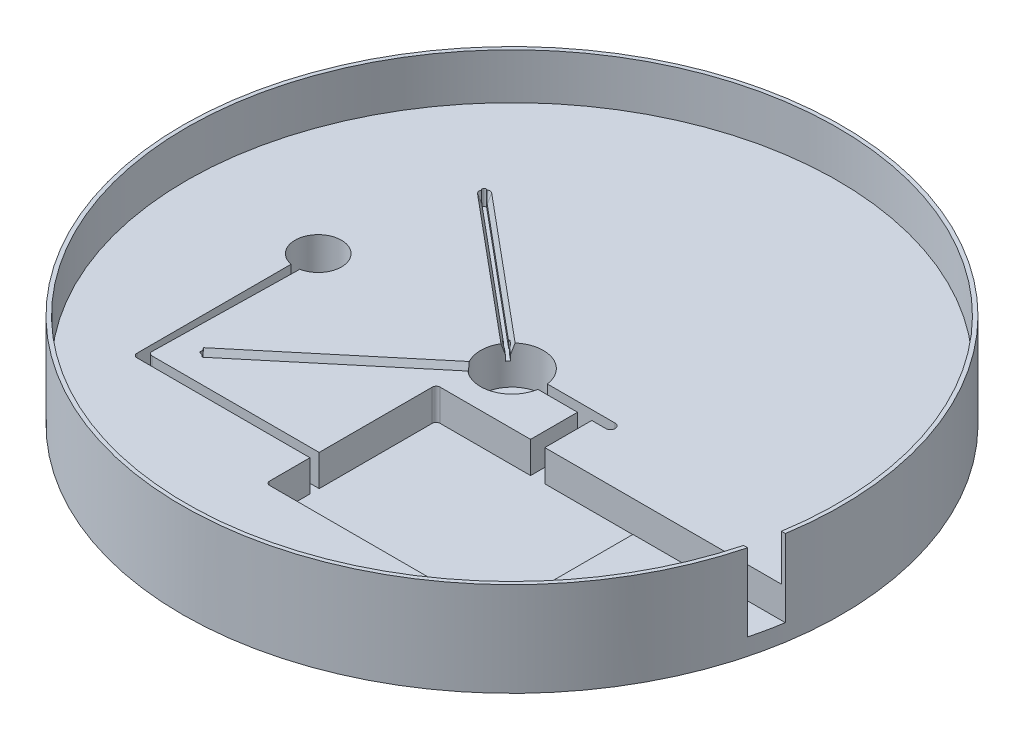
SolidWorks part; units mm, degrees
ref_plane "Front Plane" through (0, 0, 0) normal (0, 0, 1) x (1, 0, 0)
ref_plane "Top Plane" through (0, 0, 0) normal (0, 1, 0) x (1, 0, 0)
ref_plane "Right Plane" through (0, 0, 0) normal (1, 0, 0) x (0, 0, -1)
sketch "Sketch1" plane through (0, 0, 0) normal (0, 1, 0) x (1, 0, 0)
  circle A0 centre (0, 0) radius 266.7
extrude "Boss-Extrude1" add sketch "Sketch1" along normal blind 76.2
sketch "Sketch2" plane through (0, 76.2, 0) normal (0, 1, 0) x (1, 0, 0)
  circle A0 centre (0, 0) radius 263.525
extrude "Cut-Extrude1" cut sketch "Sketch2" against normal blind 37.084
sketch "Sketch3" plane through (0, 39.116, 0) normal (0, 1, 0) x (1, 0, 0)
  circle A0 centre (0, 0) radius 25.4
extrude "Cut-Extrude2" cut sketch "Sketch3" against normal blind 30.988
sketch "Sketch4" plane through (0, 39.116, 0) normal (0, 1, 0) x (1, 0, 0)
  line L0 (3.81, -0.2983) -> (80.01, -0.2983) construction
  line L1 (0, 3.5117) -> (76.2, 3.5117) construction
  line L2 (0, 3.5117) -> (0, -4.1083) construction
  line L3 (0, -4.1083) -> (76.2, -4.1083) construction
  line L4 (76.2, 3.5117) -> (76.2, -4.1083) construction
  line L5 (3.81, 3.5117) -> (80.01, 3.5117)
  line L6 (3.81, -4.1083) -> (80.01, -4.1083)
  line L7 (0, 3.5117) -> (0, -4.1083) construction
  arc A0 (3.81, 3.5117) -> (3.81, -4.1083) centre (3.81, -0.2983) ccw
  arc A1 (80.01, -4.1083) -> (80.01, 3.5117) centre (80.01, -0.2983) ccw
  point P6 (41.91, -0.2983)
extrude "Cut-Extrude3" cut sketch "Sketch4" against normal through all
sketch "Sketch5" plane through (0, 39.116, 0) normal (0, 1, 0) x (1, 0, 0)
  line L0 (0, 0) -> (-39.9134, 33.31) construction
  line L1 (-39.9134, 33.31) -> (-39.9134, -33.31) construction
  line L2 (-39.9134, 0) -> (-42.73, -2.8166) construction
  line L3 (0, 0) -> (-39.9134, 0) construction
  line L4 (-39.9134, 0) -> (-42.73, 2.8166) construction
  line L5 (0, 0) -> (-39.9134, -33.31) construction
  line L6 (0, 0) -> (-136.5075, 113.9234) construction
  line L7 (-0.9765, -1.1701) -> (-137.484, 112.7533)
  line L8 (0.9765, 1.1701) -> (-135.5311, 115.0934)
  line L13 (0, 0) -> (-136.5075, -113.9234) construction
  line L14 (-136.5075, -113.9234) -> (0, 0) construction
  line L15 (-137.484, -112.7533) -> (-0.9765, 1.1701)
  line L16 (-135.5311, -115.0934) -> (0.9765, -1.1701)
  arc A0 (-0.9765, -1.1701) -> (0.9765, 1.1701) centre (0, 0) ccw
  arc A1 (-135.5311, 115.0934) -> (-137.484, 112.7533) centre (-136.5075, 113.9234) ccw
  arc A4 (-137.484, -112.7533) -> (-135.5311, -115.0934) centre (-136.5075, -113.9234) ccw
  arc A5 (0.9765, -1.1701) -> (-0.9765, 1.1701) centre (0, 0) ccw
  point P7 (-68.2538, 56.9617)
  point P24 (-68.2538, -56.9617)
  arc M12 (25.0655, -4.1083) -> (25.1561, 3.5117) centre (0, 0) cw
extrude "Cut-Extrude4" cut sketch "Sketch5" against normal blind 12.7 contours L15 A4 L16 M12 | L7 A1 L8 A0 region at (-78.4582, 39.116, 65.4779)
ref_plane "Plane1" through (-19.4659, 0, -16.2454) normal (0.7678, 0, 0.6407) x (0.6407, 0, -0.7678)
sketch "Sketch6" plane through (-19.4659, 0, -16.2454) normal (0.7678, 0, 0.6407) x (0.6407, 0, -0.7678)
  line L0 (0, 26.416) -> (-4.0671, 39.116)
  line L1 (1.524, 26.416) -> (-1.524, 26.416) construction
  line L2 (-1.524, 39.116) -> (-24.6725, 39.116) construction
  line L3 (-4.0671, 39.116) -> (4.0671, 39.116)
  line L4 (1.524, 39.116) -> (-1.524, 39.116) construction
  line L5 (0, 39.116) -> (0, 26.416) construction
  line L6 (0, 26.416) -> (4.0671, 39.116)
extrude "Cut-Extrude5" cut sketch "Sketch6" against normal blind 152.4 and the other way blind 6.35
ref_plane "Plane2" through (-19.4659, 0, 16.2454) normal (-0.7678, 0, 0.6407) x (0.6407, 0, 0.7678)
sketch "Sketch11" plane through (-19.4659, 0, 16.2454) normal (-0.7678, 0, 0.6407) x (0.6407, 0, 0.7678)
  line L0 (0, 26.416) -> (4.7515, 39.116)
  line L1 (1.524, 26.416) -> (-1.524, 26.416) construction
  line L2 (263.525, 39.116) -> (-263.525, 39.116) construction
  line L3 (4.7515, 39.116) -> (-4.7515, 39.116)
  line L5 (0, 39.4107) -> (0, 26.416) construction
  line L7 (0, 26.416) -> (-4.7515, 39.116)
extrude "Cut-Extrude6" cut sketch "Sketch11" along normal blind 152.4 and the other way blind 6.35
ref_plane "Plane3" through (-24.3412, 0, 20.3141) normal (-0.7678, 0, 0.6407) x (0.6407, 0, 0.7678)
sketch "Sketch12" plane through (-24.3412, 0, 20.3141) normal (-0.7678, 0, 0.6407) x (0.6407, 0, 0.7678)
  line L0 (0, 26.416) -> (0, 31.0485) construction
  line L1 (1.524, 26.416) -> (-1.524, 26.416) construction
  line L2 (2.159, 26.416) -> (-2.159, 26.416) construction
  line L4 (-2.159, 26.416) -> (2.159, 26.416)
  line L7 (-2.159, 26.416) -> (-2.159, 41.4963)
  line L8 (-2.159, 41.4963) -> (2.159, 41.4963)
  line L9 (2.159, 26.416) -> (2.159, 41.4963)
extrude "Cut-Extrude10" cut sketch "Sketch12" along normal blind 6.35
ref_plane "Plane4" through (-24.3412, 0, -20.3141) normal (0.7678, 0, 0.6407) x (0.6407, 0, -0.7678)
sketch "Sketch14" plane through (-24.3412, 0, -20.3141) normal (0.7678, 0, 0.6407) x (0.6407, 0, -0.7678)
  line L0 (-2.159, 39.116) -> (2.159, 39.116) construction
  line L1 (0, 26.416) -> (-2.159, 26.416) construction
  line L2 (1.524, 26.416) -> (-1.524, 26.416) construction
  line L3 (-2.159, 26.416) -> (-2.159, 39.116) construction
  line L4 (2.159, 39.116) -> (2.159, 26.416) construction
  line L5 (2.159, 26.416) -> (0, 26.416) construction
  line L6 (0, 26.416) -> (-0.0449, 26.4266) construction
  line L8 (-2.159, 39.116) -> (2.159, 39.116)
  line L9 (-2.159, 39.116) -> (-2.159, 26.416)
  line L10 (-2.159, 26.416) -> (2.159, 26.416)
  line L11 (2.159, 39.116) -> (2.159, 26.416)
extrude "Cut-Extrude11" cut sketch "Sketch14" against normal blind 6.35
sketch "Sketch15" plane through (0, 39.116, 0) normal (0, 1, 0) x (1, 0, 0)
  line L1 (-162.497, -16.2848) -> (-162.497, -18.6107)
  line L3 (-155.4702, -16.2848) -> (-155.4702, -18.6107)
  line L4 (-162.497, -18.6107) -> (-155.4702, -18.6107)
  circle A0 centre (0, 0) radius 177.8 construction
  circle A1 centre (-159.4109, -0.0658) radius 16.9418 construction
  arc A2 (-155.4702, -16.2848) -> (-162.497, -16.2848) centre (-158.9836, 2.18) ccw
  point P6 (-158.9836, 2.18)
extrude "Cut-Extrude12" cut sketch "Sketch15" against normal blind 27.94
fillet "Fillet3" radius 3.175 1 edges at (-22.9579, 29.7868, -21.9717)
fillet "Fillet4" radius 3.175 7 edges at (-27.8331, 29.3014, 26.0404) (-30.5998, 29.3014, 22.7252) (-25.7246, 29.3014, 18.6565) (-22.9579, 29.3014, 21.9717) (-30.5998, 29.7868, -22.7252) (-27.8331, 29.7868, -26.0404) (-25.7246, 29.7868, -18.6565)
fillet "Fillet5" radius 3.175 2 edges at (-134.6812, 35.1454, -116.0404) (-138.2636, 35.1454, -111.7477)
fillet "Fillet6" radius 3.175 2 edges at (-135.4959, 34.8027, 115.0641) (-137.4489, 34.8027, 112.724)
sketch "Sketch18" plane through (0, 39.116, 0) normal (0, 1, 0) x (1, 0, 0)
  line L0 (-157.6889, -136.806) -> (-155.4702, -18.6107)
  line L1 (-19.2383, -180.0452) -> (165.1982, -180.0452)
  line L2 (-19.2383, -180.0452) -> (-19.2383, -144.2581)
  line L3 (-19.2383, -42.1099) -> (57.1594, -42.1099)
  line L4 (165.1982, -180.0452) -> (165.1982, -67.3252)
  line L5 (25.0655, -4.1083) -> (80.01, -4.1083) construction
  line L6 (68.684, -4.1083) -> (57.1594, -4.1083)
  line L7 (68.684, -4.1083) -> (68.684, -42.1099)
  line L8 (-19.2383, -136.806) -> (-19.2383, -42.1099)
  line L9 (57.1594, -4.1083) -> (57.1594, -42.1099)
  line L10 (68.684, -42.1099) -> (165.1982, -42.1099)
  line L11 (-162.497, -18.6107) -> (-157.6889, -18.6107)
  line L12 (-162.497, -18.6107) -> (-162.497, -144.2581)
  line L13 (-162.497, -144.2581) -> (-157.6889, -144.2581)
  line L14 (-155.4702, -18.6107) -> (-157.6889, -18.6107)
  line L15 (-157.6889, -144.2581) -> (-19.2383, -144.2581)
  line L17 (-157.6889, -136.806) -> (-19.2383, -136.806)
  line L18 (165.1982, -42.1099) -> (267.0856, -42.1099)
  line L20 (165.1982, -67.3252) -> (267.0856, -67.3252)
  line L21 (267.0856, -42.1099) -> (267.0856, -67.3252)
extrude "Cut-Extrude13" cut sketch "Sketch18" against normal blind 25.4 and the other way through all
fillet "Fillet8" radius 3.175 5 edges at (165.1982, 26.416, 180.0452) (-19.2383, 26.416, 42.1099) (-19.2383, 26.416, 180.0452) (-162.497, 26.416, 144.2581) (-157.6889, 26.416, 136.806)
